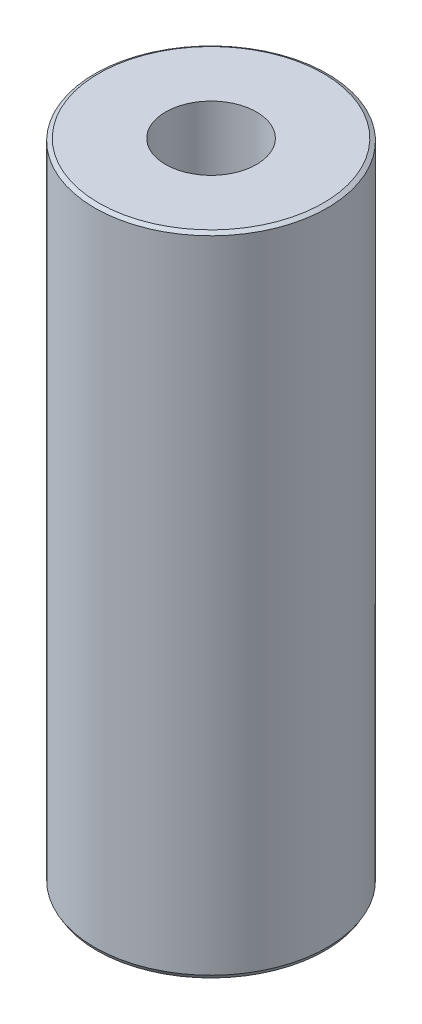
SolidWorks part; units mm, degrees
ref_plane "Front Plane" through (0, 0, 0) normal (0, 0, 1) x (1, 0, 0)
ref_plane "Top Plane" through (0, 0, 0) normal (0, 1, 0) x (1, 0, 0)
ref_plane "Right Plane" through (0, 0, 0) normal (1, 0, 0) x (0, 0, -1)
sketch "Sketch1" plane through (0, 0, 0) normal (0, 1, 0) x (1, 0, 0)
  circle A0 centre (0, 0) radius 47.5
  dimension "SHAFT_OD" = 95
extrude "Boss-Extrude1" add sketch "Sketch1" along normal blind 264.1783
sketch "Sketch2" plane through (0, 0, 0) normal (0, 1, 0) x (1, 0, 0)
  circle A0 centre (0, 0) radius 18.595
  dimension "BORE_D" = 37.19
extrude "Cut-Extrude1" cut sketch "Sketch2" along normal through all
chamfer "Chamfer1" distance 0.9421 angle 60 2 edges at (0, 264.1783, 47.5) (0, 0, 47.5) first distance on face at (0, 264.1783, 47.5) first distance on face at (0, 0, 18.595)
